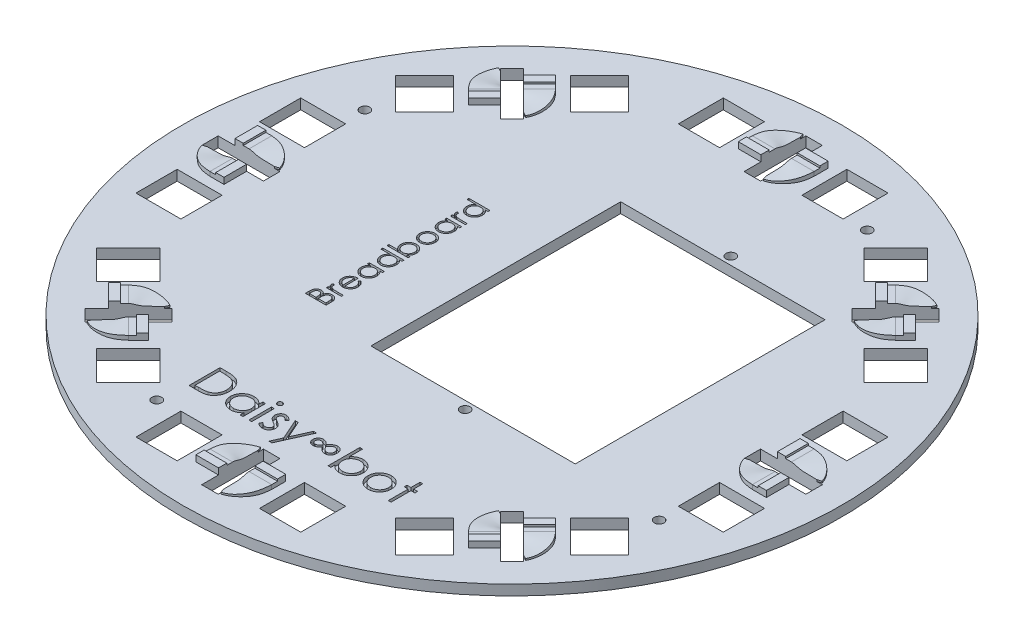
SolidWorks part; units mm, degrees
ref_plane "Front" through (0, 0, 0) normal (0, 0, 1) x (1, 0, 0)
ref_plane "Top" through (0, 0, 0) normal (0, 1, 0) x (1, 0, 0)
ref_plane "Right" through (0, 0, 0) normal (1, 0, 0) x (0, 0, -1)
sketch "Sketch1" plane through (0, 0, 0) normal (0, 1, 0) x (1, 0, 0)
  circle A0 centre (0, 0) radius 101.6
  dimension "D1" = 203.2
extrude "Base" add sketch "Sketch1" along normal blind 3.175 contours A0
sketch "Sketch2" plane through (0, 3.175, 0) normal (0, 1, 0) x (1, 0, 0)
  line L1 (-2.54, -93.1333) -> (2.54, -93.1333)
  line L2 (-2.54, -93.1333) -> (-2.54, -74.0833)
  line L3 (-2.54, -74.0833) -> (2.54, -74.0833)
  line L4 (2.54, -93.1333) -> (2.54, -74.0833)
  point P4 (0, -74.0833)
  dimension "D1" = 5.08
  dimension "D2" = 19.05
  dimension "D3" = 93.1333
extrude "Cut-Extrude1" cut sketch "Sketch2" against normal up to next and the other way through all contours L1 L4 L3 L2
sketch "Sketch4" plane through (0, 3.175, 0) normal (0, 1, 0) x (1, 0, 0)
  line L0 (0, -83.6083) -> (-2.9434, -74.5495) construction
  line L1 (-2.9434, -74.5495) -> (0, -83.6083) construction
  line L2 (0, -83.6083) -> (-5.5987, -75.9024) construction
  line L3 (0, -83.6083) -> (-7.7059, -78.0097) construction
  line L4 (0, -83.6083) -> (-9.0588, -80.6649) construction
  line L5 (0, -83.6083) -> (-9.525, -83.6083) construction
  line L9 (2.54, -74.0833) -> (-2.54, -74.0833) construction
  line L10 (2.54, -74.0833) -> (2.54, -93.1333) construction
  line L11 (-2.54, -74.0833) -> (-2.54, -93.1333) construction
  line L12 (2.54, -93.1333) -> (-2.54, -93.1333) construction
  circle A0 centre (0, -83.6083) radius 9.525 construction
  point P16 (0, -74.0833)
  point P19 (2.54, -83.6083)
  dimension "D1" = 18
  dimension "D2" = 18
  dimension "D3" = 18
  dimension "D4" = 18
  dimension "D5" = 18
ref_plane "Plane1" through (-24.5719, 0, 7.9839) normal (0.9511, 0, -0.309) x (-0.309, 0, -0.9511)
ref_plane "Plane2" through (-39.7581, 0, 28.886) normal (0.809, 0, -0.5878) x (-0.5878, 0, -0.809)
ref_plane "Plane3" through (-39.7581, 0, 54.7224) normal (0.5878, 0, -0.809) x (-0.809, 0, -0.5878)
ref_plane "Plane4" through (-24.5719, 0, 75.6244) normal (0.309, 0, -0.9511) x (-0.9511, 0, -0.309)
ref_plane "Plane5" through (0, 0, 83.6083) normal (0, 0, -1) x (-1, 0, 0)
sketch "Sketch5" plane through (-24.5719, 0, 7.9839) normal (0.9511, 0, -0.309) x (-0.309, 0, -0.9511)
  line L0 (-69.6725, 3.175) -> (-87.7902, 3.175) construction
  line L1 (-71.2966, 3.175) -> (-69.9913, 3.175)
  line L2 (-71.2966, 3.175) -> (-71.2966, 3.683)
  line L3 (-71.2966, 3.683) -> (-69.9913, 3.683)
  line L4 (-69.9913, 3.175) -> (-69.9913, 3.683)
  dimension "D2" = 0.508
sketch "Sketch6" plane through (-39.7581, 0, 28.886) normal (0.809, 0, -0.5878) x (-0.5878, 0, -0.809)
  line L0 (-58.4417, 3.175) -> (-73.8535, 3.175) construction
  line L1 (-63.3193, 3.175) -> (-58.1156, 3.175)
  line L2 (-63.3193, 3.175) -> (-63.3193, 3.775)
  line L3 (-63.3193, 3.775) -> (-58.1156, 3.775)
  line L4 (-58.1156, 3.175) -> (-58.1156, 3.775)
  dimension "D2" = 0.6
sketch "Sketch7" plane through (-39.7581, 0, 54.7224) normal (0.5878, 0, -0.809) x (-0.809, 0, -0.5878)
  line L0 (-41.4902, 3.175) -> (-52.6875, 3.175) construction
  line L1 (-46.0041, 3.175) -> (-39.6187, 3.175)
  line L2 (-46.0041, 3.175) -> (-46.0041, 4.075)
  line L3 (-46.0041, 4.075) -> (-39.6187, 4.075)
  line L4 (-39.6187, 3.175) -> (-39.6187, 4.075)
  dimension "D2" = 0.9
sketch "Sketch10" plane through (-24.5719, 0, 75.6244) normal (0.309, 0, -0.9511) x (-0.9511, 0, -0.309)
  line L0 (-25.8364, 3.175) -> (-16.7776, 3.175) construction
  line L1 (-23.1657, 3.175) -> (-16.3114, 3.175)
  line L2 (-23.1657, 3.175) -> (-23.1657, 4.375)
  line L3 (-23.1657, 4.375) -> (-16.3114, 4.375)
  line L4 (-16.3114, 3.175) -> (-16.3114, 4.375)
  dimension "D3" = 1.2
sketch "Sketch11" plane through (0, 0, 83.6083) normal (0, 0, -1) x (-1, 0, 0)
  line L0 (0, 3.175) -> (9.525, 3.175) construction
  line L1 (2.54, 3.175) -> (9.525, 3.175)
  line L2 (2.54, 3.175) -> (2.54, 4.475)
  line L3 (2.54, 4.475) -> (9.525, 4.475)
  line L4 (9.525, 3.175) -> (9.525, 4.475)
  dimension "D3" = 1.3
loft "Loft1" add profiles "Sketch5", "Sketch6", "Sketch7", "Sketch10", "Sketch11" connector at (-2.54, 3.683, 75.791) connector at (-2.54, 3.775, 80.1123) connector at (-2.54, 4.075, 81.7629) connector at (-2.54, 4.375, 82.783) connector at (-2.54, 4.475, 83.6083)
sketch "Sketch13" plane through (-104.9799, 0, 83.6083) normal (0, 0, -1) x (-1, 0, 0)
  line L6 (-95.4549, 3.175) -> (-102.4399, 3.175)
  line L7 (-95.4549, 3.175) -> (-95.4549, 4.475)
  line L8 (-95.4549, 4.475) -> (-102.4399, 4.475)
  line L9 (-102.4399, 3.175) -> (-102.4399, 4.475)
extrude "Boss-Extrude4" add sketch "Sketch13" against normal blind 1.7907
sketch "Sketch25" plane through (0, 0, 85.399) normal (0, 0, 1) x (1, 0, 0)
  line L0 (-9.525, 4.475) -> (-2.54, 4.475) construction
  line L1 (-9.525, 3.175) -> (-2.54, 3.175)
  line L2 (-9.525, 3.175) -> (-9.525, 5.075)
  line L3 (-9.525, 5.075) -> (-2.54, 5.075)
  line L4 (-2.54, 3.175) -> (-2.54, 5.075)
  dimension "D1" = 0.6
extrude "Boss-Extrude5" add sketch "Sketch25" along normal blind 2.54
sketch "Sketch14" plane through (-2.54, 0, 0) normal (1, 0, 0) x (0, 0, -1)
  line L0 (-83.6083, 3.175) -> (-83.6083, 0) construction
  line L1 (-74.0833, 0) -> (-93.1333, 0) construction
ref_plane "Plane6" through (0, 0, 0) normal (1, 0, 0) x (0, 0, -1)
sketch "Sketch15" plane through (0, 0, 0) normal (1, 0, 0) x (0, 0, -1)
  line L0 (-83.6083, 0) -> (-83.6083, 3.175) construction
pattern_circular "CirPattern1" count 2 over 360 about axis through (0, 0, 83.6083) along (0, 1, 0) of "Loft1", "Boss-Extrude5", "Boss-Extrude4" reverse direction yes
ref_axis "Axis1" through (0, 50, 0) along (0, -1, 0)
pattern_circular "CirPattern5" count 8 over 360 about axis through (0, 50, 0) along (0, -1, 0) of "CirPattern1", "Cut-Extrude1"
sketch "Sketch18" plane through (0, 3.175, 0) normal (0, 1, 0) x (1, 0, 0)
  line L4 (0, -101.6) -> (0, 101.6) construction
  line L5 (0, -1.7463) -> (0, 1.7463) construction
  line L9 (-13.5, -30) -> (49.5, -30)
  line L10 (-13.5, -30) -> (-13.5, 47)
  line L11 (-13.5, 47) -> (49.5, 47)
  line L12 (49.5, -30) -> (49.5, 47)
  circle A8 centre (0, 0) radius 101.6 construction
  point P0 (0, 0)
  dimension "D1" = 13.5
  dimension "D2" = 47
  dimension "D3" = 77
  dimension "D4" = 63
sketch "Sketch19" plane through (0, 3.175, 0) normal (0, 1, 0) x (1, 0, 0)
  line L0 (-32.0765, -77.4396) -> (0, 0) construction
  line L1 (0, -101.6) -> (0, 101.6) construction
  circle A1 centre (-32.0765, -77.4396) radius 1.5
  circle A4 centre (0, 0) radius 101.6 construction
  dimension "D4" = 3
  dimension "D6" = 83.82
  dimension "D5" = 22.5
extrude "Cut-Extrude2" cut sketch "Sketch19" against normal through all
pattern_circular "CirPattern7" count 4 over 360 about axis through (0, 50, 0) along (0, -1, 0) of "Cut-Extrude2"
sketch "Sketch23" plane through (0, 3.175, 0) normal (0, 1, 0) x (1, 0, 0)
  line L9 (-2.54, -87.939) -> (-2.54, -93.1333) construction
  line L10 (-25.4, -76.6805) -> (-12.7, -76.6805)
  line L11 (-25.4, -76.6805) -> (-25.4, -90.5362)
  line L16 (-25.4, -90.5362) -> (-12.7, -90.5362)
  line L17 (-12.7, -76.6805) -> (-12.7, -90.5362)
  line L19 (2.54, -74.0833) -> (2.54, -79.2776) construction
  line L20 (0, -50) -> (0, 50) construction
  line L21 (12.7, -76.6805) -> (12.7, -90.5362)
  line L22 (25.4, -90.5362) -> (12.7, -90.5362)
  line L23 (25.4, -76.6805) -> (25.4, -90.5362)
  line L24 (25.4, -76.6805) -> (12.7, -76.6805)
  point P8 (-2.54, -90.5362)
  point P9 (2.54, -76.6805)
  dimension "D1" = 12.7
  dimension "D2" = 10.16
extrude "Cut-Extrude6" cut sketch "Sketch23" against normal through all
pattern_circular "CirPattern8" count 8 over 360 about axis through (0, 50, 0) along (0, -1, 0) of "Cut-Extrude6"
sketch "Sketch17" plane through (0, 3.175, 0) normal (0, 1, 0) x (1, 0, 0)
  line L0 (33.02, -68.58) -> (-33.02, -68.58) construction
  line L1 (2.54, -74.0833) -> (-2.54, -74.0833) construction
  point P3 (0, -68.58)
  point P7 (0, -74.0833)
  dimension "D2" = 68.58
  dimension "D1" = 66.04
sketch "Sketch16" plane through (0, 3.175, 0) normal (0, 1, 0) x (1, 0, 0)
  line L0 (33.02, -68.58) -> (-33.02, -68.58) construction
  text T0 "Daisy∞bot\r\n" font "Century Gothic" height in points 36
extrude "Cut-Extrude4" cut sketch "Sketch16" against normal blind 1.27
sketch "Sketch22" plane through (0, 3.175, 0) normal (0, 1, 0) x (1, 0, 0)
  line L0 (-31.3017, 25.1735) -> (-31.3017, -33.6024) construction
  text T0 "Breadboard"
extrude "Cut-Extrude5" cut sketch "Sketch22" against normal blind 1.27
extrude "Cut-Extrude7" cut sketch "Sketch18" against normal through all
ref_plane "Plane7" through (0, 0, -8.5) normal (0, 0, 1) x (1, 0, 0)
sketch "Sketch26" plane through (0, 3.175, 0) normal (0, 1, 0) x (1, 0, 0)
  line L0 (-13.5, -30) -> (49.5, -30) construction
  line L3 (-50, 8.5) -> (50, 8.5) construction
  circle A0 centre (18, -32.45) radius 1.5
  circle A3 centre (18, 49.45) radius 1.5
  point P4 (18, -30)
  dimension "D1" = 3
  dimension "D2" = 2.45
extrude "Cut-Extrude8" cut sketch "Sketch26" against normal through all
